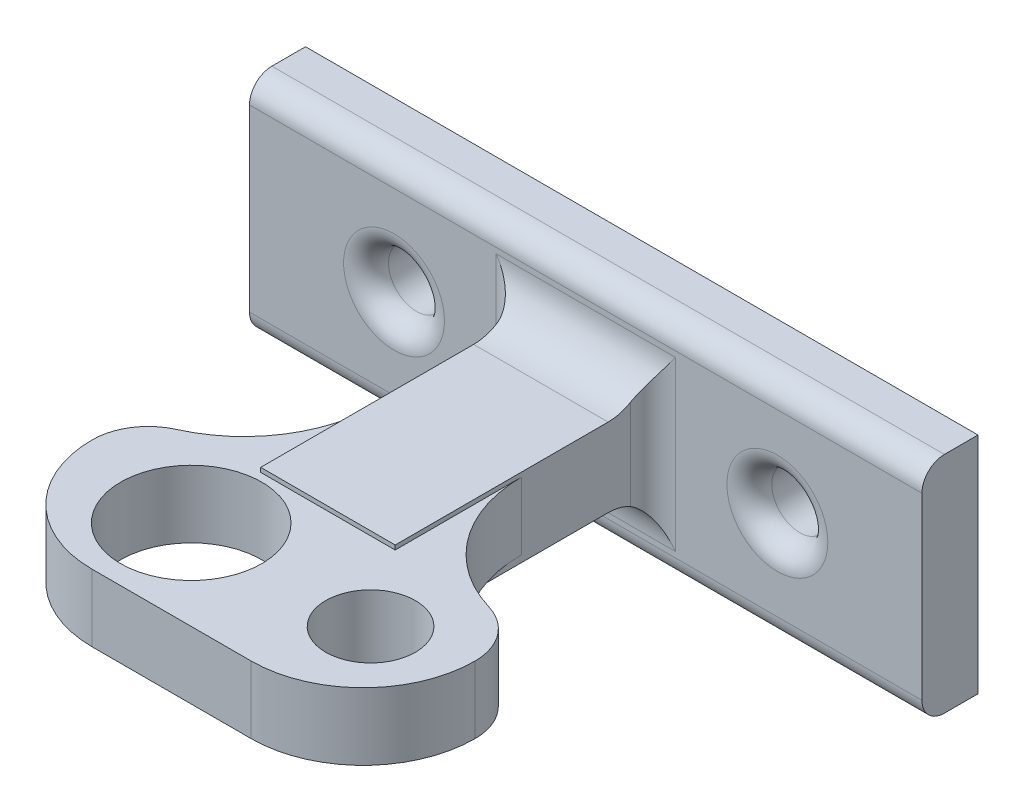
SolidWorks part; units mm, degrees
ref_plane "Plano frontal" through (0, 0, 0) normal (0, 0, 1) x (1, 0, 0)
ref_plane "Plano superior" through (0, 0, 0) normal (0, 1, 0) x (1, 0, 0)
ref_plane "Plano direito" through (0, 0, 0) normal (1, 0, 0) x (0, 0, -1)
sketch "Esboço1" plane through (0, 0, 0) normal (0, 0, 1) x (1, 0, 0)
  line L0 (-26.3736, -0.1099) -> (33.6264, -0.1099) construction
  line L1 (-26.3736, 9.8901) -> (33.6264, 9.8901)
  line L2 (-26.3736, 9.8901) -> (-26.3736, -10.1099)
  line L3 (-26.3736, -10.1099) -> (33.6264, -10.1099)
  line L4 (33.6264, 9.8901) -> (33.6264, -10.1099)
  line L6 (3.6264, 9.8901) -> (3.6264, -10.1099) construction
  circle A0 centre (-13.4736, -0.1099) radius 2.5
  circle A1 centre (20.7264, -0.1099) radius 2.5
  dimension "D5" = 5
  dimension "D6" = 5
  dimension "D1" = 60
  dimension "D2" = 20
  dimension "D3" = 17.1
  dimension "D4" = 17.1
extrude "Ressalto-extrusão2" add sketch "Esboço1" along normal blind 5
sketch "Esboço2" plane through (0, 0, 0) normal (0, 0, 1) x (1, 0, 0)
  line L0 (3.6264, 9.8901) -> (3.6264, -10.1099) construction
  line L1 (33.6264, 9.8901) -> (-26.3736, 9.8901) construction
  line L2 (-26.3736, -10.1099) -> (33.6264, -10.1099) construction
  line L3 (-26.3736, -0.1099) -> (33.6264, -0.1099) construction
  line L4 (-26.3736, 9.8901) -> (-26.3736, -10.1099) construction
  line L5 (33.6264, -10.1099) -> (33.6264, 9.8901) construction
  line L7 (-2.3736, 3.3901) -> (9.6264, 3.3901)
  line L8 (-2.3736, 3.3901) -> (-2.3736, -3.6099)
  line L9 (-2.3736, -3.6099) -> (9.6264, -3.6099)
  line L10 (9.6264, 3.3901) -> (9.6264, -3.6099)
  dimension "D1" = 7
  dimension "D2" = 3.5
  dimension "D3" = 12
  dimension "D4" = 6
extrude "Ressalto-extrusão3" add sketch "Esboço2" along normal blind 28
sketch "Esboço3" plane through (0, 0, 0) normal (0, 1, 0) x (1, 0, 0)
  line L0 (-2.3736, -28) -> (-11.0661, -28) construction
  line L2 (3.6264, 0) -> (3.6264, -43) construction
  line L3 (-11.0661, -28) -> (20.4284, -28)
  line L5 (-21.3736, -43) -> (28.6264, -43)
  line L7 (33.6264, 0) -> (-26.3736, 0) construction
  line L8 (-11.0661, -28) -> (-21.3736, -43)
  line L9 (-21.3736, -43) -> (28.6264, -43)
  line L10 (28.6264, -43) -> (20.4284, -28)
  line L12 (-11.0661, -28) -> (20.4284, -28) construction
  circle A0 centre (-1.5716, -35) radius 6.3
  circle A1 centre (14.4284, -35) radius 4
  dimension "D2" = 12.6
  dimension "D6" = 8
  dimension "D1" = 16
  dimension "D3" = 0
  dimension "D4" = 30
  dimension "D5" = 22
extrude "Ressalto-extrusão4" add sketch "Esboço3" along normal blind 3 and the other way blind 3 contours L5 L10 L3 L8 A1 A0
fillet "Filete1" radius 10 1 edges at (-21.3736, 0, 43)
fillet "Filete2" radius 10 1 edges at (28.6264, 0, 43)
fillet "Filete5" radius 5 1 edges at (20.4284, 0, 28)
fillet "Filete7" radius 5 1 edges at (-11.0661, 0, 28)
fillet "Filete9" radius 2 1 edges at (9.6264, -0.1099, 5)
fillet "Filete10" radius 2 1 edges at (-2.3736, -0.1099, 5)
fillet "Filete13" radius 12 1 edges at (-2.3736, 0, 28)
fillet "Filete14" radius 12 1 edges at (9.6264, 0, 28)
fillet "Filete15" radius 4 1 edges at (3.6264, 3.3901, 5)
fillet "Filete16" radius 4 1 edges at (3.6264, -3.6099, 5)
fillet "Filete17" radius 2 1 edges at (23.2264, -0.1099, 5)
fillet "Filete18" radius 2 1 edges at (-10.9736, -0.1099, 5)
fillet "Filete19" radius 2 1 edges at (3.6264, 9.8901, 5)
fillet "Filete20" radius 2 1 edges at (3.6264, -10.1099, 5)
